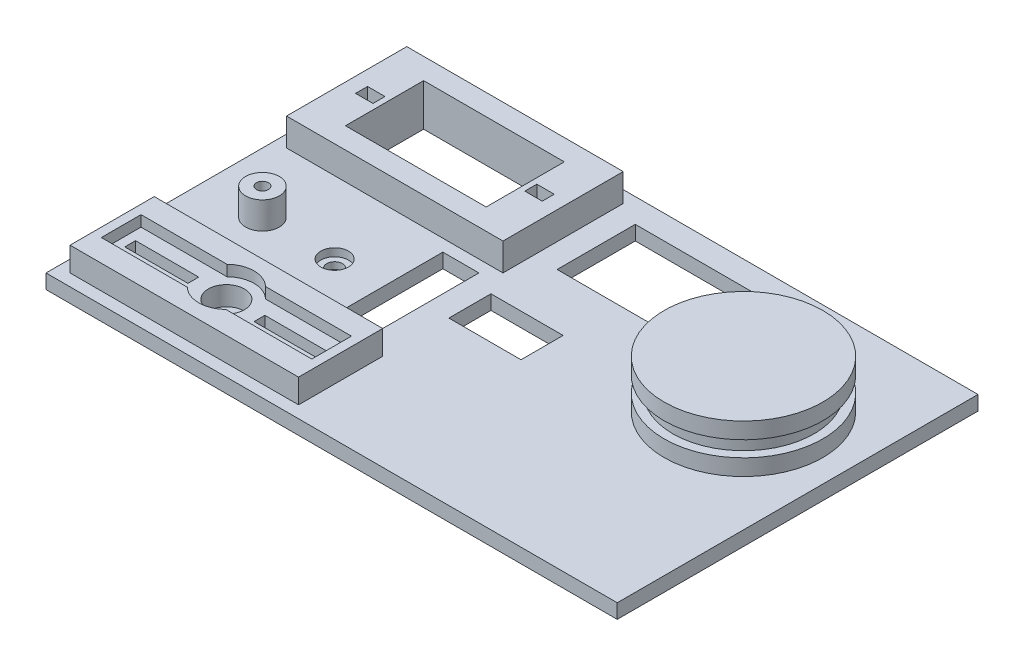
SolidWorks part; units mm, degrees
ref_plane "Front Plane" through (0, 0, 0) normal (0, 0, 1) x (1, 0, 0)
ref_plane "Top Plane" through (0, 0, 0) normal (0, 1, 0) x (1, 0, 0)
ref_plane "Right Plane" through (0, 0, 0) normal (1, 0, 0) x (0, 0, -1)
sketch "Sketch1" plane through (0, 0, 0) normal (0, 0, 1) x (1, 0, 0)
  line L1 (150, 0) -> (245, 0)
  line L2 (150, 0) -> (150, 2.4)
  line L3 (150, 2.4) -> (245, 2.4)
  line L4 (245, 0) -> (245, 2.4)
extrude "Boss-Extrude1" add sketch "Sketch1" along normal blind 60
sketch "Sketch2" plane through (0, 0, 0) normal (0, 0, 1) x (1, 0, 0)
  line L1 (152, 2.4) -> (188, 2.4)
  line L2 (152, 2.4) -> (152, 7)
  line L3 (152, 7) -> (188, 7)
  line L4 (188, 2.4) -> (188, 7)
extrude "Boss-Extrude2" add sketch "Sketch2" along normal blind 20 from offset 2
sketch "Sketch3" plane through (0, 0, 0) normal (0, 0, 1) x (1, 0, 0)
  line L1 (158.3, -1) -> (181.7, -1)
  line L2 (158.3, -1) -> (158.3, 8)
  line L3 (158.3, 8) -> (181.7, 8)
  line L4 (181.7, -1) -> (181.7, 8)
extrude "Boss-Extrude3" add sketch "Sketch3" along normal blind 13 from offset 5.5 separate body
combine bodies "Combine1" operation type subtract main body 102 bodies to subtract 103
sketch "Sketch4" plane through (0, 0, 0) normal (0, 0, 1) x (1, 0, 0)
  line L1 (154.475, -1) -> (157.375, -1)
  line L2 (154.475, -1) -> (154.475, 8)
  line L3 (154.475, 8) -> (157.375, 8)
  line L4 (157.375, -1) -> (157.375, 8)
extrude "Boss-Extrude4" add sketch "Sketch4" along normal blind 2 from offset 11 separate body
combine bodies "Combine2" operation type subtract main body 104 bodies to subtract 105
sketch "Sketch5" plane through (0, 0, 0) normal (0, 0, 1) x (1, 0, 0)
  line L1 (182.625, -1) -> (185.525, -1)
  line L2 (182.625, -1) -> (182.625, 8)
  line L3 (182.625, 8) -> (185.525, 8)
  line L4 (185.525, -1) -> (185.525, 8)
extrude "Boss-Extrude5" add sketch "Sketch5" along normal blind 2 from offset 11 separate body
combine bodies "Combine3" operation type subtract main body 106 bodies to subtract 107
sketch "Sketch6" plane through (0, 0, 0) normal (0, 0, 1) x (1, 0, 0)
  line L1 (192, -1) -> (211.4, -1)
  line L2 (192, -1) -> (192, 3.4)
  line L3 (192, 3.4) -> (211.4, 3.4)
  line L4 (211.4, -1) -> (211.4, 3.4)
extrude "Boss-Extrude6" add sketch "Sketch6" along normal blind 13 from offset 4 separate body
combine bodies "Combine4" operation type subtract main body 108 bodies to subtract 109
sketch "Sketch7" plane through (0, 0, 0) normal (0, 1, 0) x (1, 0, 0)
  circle A0 centre (160, -34) radius 2.8
extrude "Boss-Extrude7" add sketch "Sketch7" along normal blind 4.5 from offset 2.4
sketch "Sketch8" plane through (0, 0, 0) normal (0, 1, 0) x (1, 0, 0)
  circle A0 centre (160, -34) radius 1
extrude "Boss-Extrude8" add sketch "Sketch8" along normal blind 6.3 from offset 1.6 separate body
combine bodies "Combine5" operation type subtract main body 111 bodies to subtract 112
sketch "Sketch9" plane through (0, 0, 0) normal (0, 1, 0) x (1, 0, 0)
  circle A0 centre (172, -34) radius 1.3
extrude "Boss-Extrude9" add sketch "Sketch9" along normal blind 4.4 from offset 1 separate body offset against normal yes
combine bodies "Combine6" operation type subtract main body 113 bodies to subtract 114
sketch "Sketch10" plane through (0, 0, 0) normal (0, 1, 0) x (1, 0, 0)
  circle A0 centre (172, -34) radius 2.3
extrude "Boss-Extrude10" add sketch "Sketch10" along normal blind 2.3 from offset 1.1 separate body
combine bodies "Combine7" operation type subtract main body 115 bodies to subtract 116
sketch "Sketch11" plane through (0, 0, 0) normal (0, 0, 1) x (1, 0, 0)
  line L1 (180, -1) -> (186, -1)
  line L2 (180, -1) -> (180, 3.4)
  line L3 (180, 3.4) -> (186, 3.4)
  line L4 (186, -1) -> (186, 3.4)
extrude "Boss-Extrude11" add sketch "Sketch11" along normal blind 17 from offset 24 separate body
combine bodies "Combine8" operation type subtract main body 117 bodies to subtract 118
sketch "Sketch12" plane through (0, 0, 0) normal (0, 0, 1) x (1, 0, 0)
  line L1 (190, -1) -> (202, -1)
  line L2 (190, -1) -> (190, 3.4)
  line L3 (190, 3.4) -> (202, 3.4)
  line L4 (202, -1) -> (202, 3.4)
extrude "Boss-Extrude12" add sketch "Sketch12" along normal blind 7 from offset 26 separate body
combine bodies "Combine9" operation type subtract main body 119 bodies to subtract 120
sketch "Sketch13" plane through (0, 0, 0) normal (0, 1, 0) x (1, 0, 0)
  circle A0 centre (228, -22) radius 13.2
extrude "Boss-Extrude13" add sketch "Sketch13" along normal blind 8 from offset 2.4
sketch "Sketch14" plane through (0, 0, 0) normal (0, 1, 0) x (1, 0, 0)
  circle A0 centre (228, -22) radius 20
extrude "Boss-Extrude14" add sketch "Sketch14" along normal blind 2.6 from offset 5.1 separate body
combine bodies "Combine10" operation type subtract main body 122 bodies to subtract 123
sketch "Sketch15" plane through (0, 0, 0) normal (0, 1, 0) x (1, 0, 0)
  circle A0 centre (228, -22) radius 11.75
extrude "Boss-Extrude15" add sketch "Sketch15" along normal blind 2.6 from offset 5.1
sketch "Sketch16" plane through (0, 0, 0) normal (0, 0, 1) x (1, 0, 0)
  line L1 (152, 2.4) -> (190, 2.4)
  line L2 (152, 2.4) -> (152, 6.4)
  line L3 (152, 6.4) -> (190, 6.4)
  line L4 (190, 2.4) -> (190, 6.4)
extrude "Boss-Extrude16" add sketch "Sketch16" along normal blind 14 from offset 44
sketch "Sketch17" plane through (0, 0, 0) normal (0, 1, 0) x (1, 0, 0)
  circle A0 centre (171, -51) radius 4.6
extrude "Boss-Extrude17" add sketch "Sketch17" along normal blind 2.3 from offset 4.6 separate body
combine bodies "Combine11" operation type subtract main body 127 bodies to subtract 128
sketch "Sketch18" plane through (0, 0, 0) normal (0, 0, 1) x (1, 0, 0)
  line L1 (171, 4.6) -> (188.5, 4.6)
  line L2 (171, 4.6) -> (171, 6.9)
  line L3 (171, 6.9) -> (188.5, 6.9)
  line L4 (188.5, 4.6) -> (188.5, 6.9)
extrude "Boss-Extrude18" add sketch "Sketch18" along normal blind 6.6 from offset 47.7 separate body
combine bodies "Combine12" operation type subtract main body 129 bodies to subtract 130
sketch "Sketch19" plane through (0, 0, 0) normal (0, 0, 1) x (1, 0, 0)
  line L1 (176.5, 1.4) -> (187, 1.4)
  line L2 (176.5, 1.4) -> (176.5, 7.4)
  line L3 (176.5, 7.4) -> (187, 7.4)
  line L4 (187, 1.4) -> (187, 7.4)
extrude "Boss-Extrude19" add sketch "Sketch19" along normal blind 1.8 from offset 50.1 separate body
combine bodies "Combine13" operation type subtract main body 131 bodies to subtract 132
sketch "Sketch20" plane through (0, 0, 0) normal (0, 0, 1) x (1, 0, 0)
  line L1 (153.5, 4.6) -> (171, 4.6)
  line L2 (153.5, 4.6) -> (153.5, 6.9)
  line L3 (153.5, 6.9) -> (171, 6.9)
  line L4 (171, 4.6) -> (171, 6.9)
extrude "Boss-Extrude20" add sketch "Sketch20" along normal blind 6.6 from offset 47.7 separate body
combine bodies "Combine14" operation type subtract main body 133 bodies to subtract 134
sketch "Sketch21" plane through (0, 0, 0) normal (0, 0, 1) x (1, 0, 0)
  line L1 (155, 1.4) -> (165.5, 1.4)
  line L2 (155, 1.4) -> (155, 7.4)
  line L3 (155, 7.4) -> (165.5, 7.4)
  line L4 (165.5, 1.4) -> (165.5, 7.4)
extrude "Boss-Extrude21" add sketch "Sketch21" along normal blind 1.8 from offset 50.1 separate body
combine bodies "Combine15" operation type subtract main body 135 bodies to subtract 136
sketch "Sketch22" plane through (0, 0, 0) normal (0, 1, 0) x (1, 0, 0)
  circle A0 centre (171, -51) radius 3
extrude "Boss-Extrude22" add sketch "Sketch22" along normal blind 6 from offset 1.4 separate body
combine bodies "Combine16" operation type subtract main body 137 bodies to subtract 138
